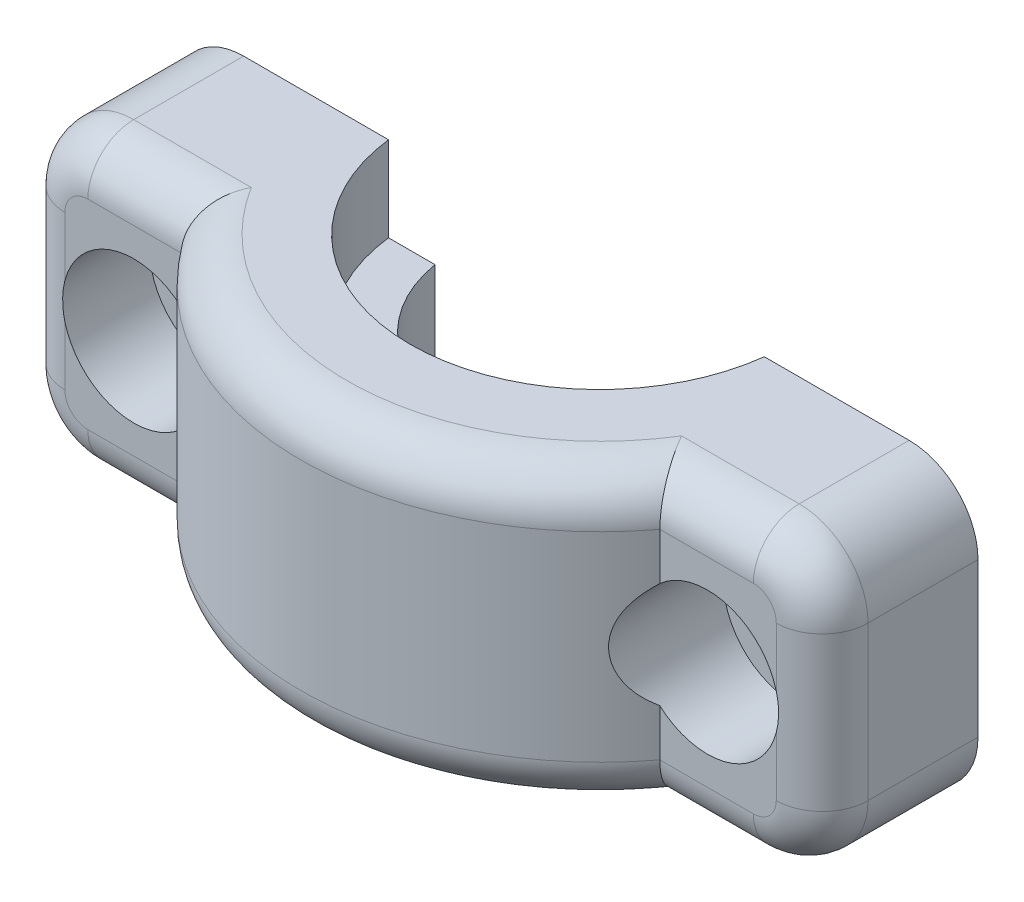
SolidWorks part; units mm, degrees
material "ABS"
ref_plane "Front Plane" through (0, 0, 0) normal (0, 0, 1) x (1, 0, 0)
ref_plane "Top Plane" through (0, 0, 0) normal (0, 1, 0) x (1, 0, 0)
ref_plane "Right Plane" through (0, 0, 0) normal (1, 0, 0) x (0, 0, -1)
sketch "Sketch1" plane through (0, 0, 0) normal (0, 0, 1) x (1, 0, 0)
  line L1 (-17.5, -6.35) -> (17.5, -6.35)
  line L2 (-17.5, -6.35) -> (-17.5, 6.35)
  line L3 (-17.5, 6.35) -> (17.5, 6.35)
  line L4 (17.5, -6.35) -> (17.5, 6.35)
  line L5 (-17.5, -6.35) -> (17.5, 6.35) construction
  line L6 (-17.5, 6.35) -> (17.5, -6.35) construction
  circle A0 centre (12.5, 0) radius 1.75
  circle A1 centre (-12.5, 0) radius 1.75
  point P0 (0, 0)
  dimension "D1" = 12.5
  dimension "D2" = 25
  dimension "D5" = 3.5
  dimension "D3" = 35
  dimension "D4" = 12.7
extrude "Boss-Extrude1" add sketch "Sketch1" along normal blind 12
sketch "Sketch2" plane through (0, 6.35, 0) normal (0, 1, 0) x (1, 0, 0)
  line L0 (17.5, 0) -> (-17.5, 0) construction
  circle A0 centre (0, 1) radius 8.25
  dimension "D2" = 16.5
  dimension "D1" = 1
extrude "Cut-Extrude1" cut sketch "Sketch2" against normal blind 3.7
sketch "Sketch3" plane through (0, 2.65, 0) normal (0, 1, 0) x (1, 0, 0)
  circle A0 centre (0, 1.0412) radius 6.25
  dimension "D1" = 12.5
extrude "Cut-Extrude2" cut sketch "Sketch3" against normal blind 5.7
sketch "Sketch4" plane through (0, -3.05, 0) normal (0, 1, 0) x (1, 0, 0)
  circle A0 centre (0, 1.0412) radius 8.25
  dimension "D1" = 16.5
extrude "Cut-Extrude3" cut sketch "Sketch4" against normal blind 6
sketch "Sketch5" plane through (0, 0, 12) normal (0, 0, 1) x (1, 0, 0)
  circle A0 centre (-12.5, 0) radius 3.1
  circle A1 centre (12.5, 0) radius 3.1
  dimension "D1" = 6.2
  dimension "D2" = 6.2
extrude "Cut-Extrude4" cut sketch "Sketch5" against normal offset from surface (9 mm away) 3 up to face at (10.009, -0.1, 0)
sketch "Sketch6" plane through (0, -6.35, 0) normal (0, -1, 0) x (1, 0, 0)
  line L0 (17.5, 0) -> (0, 0)
  line L1 (17.5, 0) -> (17.5, 6.7912)
  line L2 (17.5, 12) -> (17.5, 0) construction
  line L3 (17.5, 6.7912) -> (10.4272, 6.7912)
  line L4 (-17.5, 12) -> (-17.5, 0) construction
  line L5 (-17.5, 6.7912) -> (-17.5, 0)
  line L6 (-17.5, 0) -> (0, 0)
  line L7 (-10.4272, 6.7912) -> (-17.5, 6.7912)
  line L8 (-17.5, 12) -> (17.5, 12) construction
  line L9 (17.5, 6.7912) -> (17.5, 12)
  line L10 (17.5, 12) -> (-17.5, 12)
  line L11 (-17.5, 12) -> (-17.5, 6.7912)
  arc A0 (10.4272, 6.7912) -> (-10.4272, 6.7912) centre (0, -1.0412) ccw
  arc A3 (6.1627, 0) -> (-6.1627, 0) centre (0, -1.0412) ccw construction
  line M8 (17.5, 0) -> (17.5, 12)
  line M9 (17.5, 12) -> (-17.5, 12)
  line M10 (-17.5, 12) -> (-17.5, 0)
  dimension "D1" = 6.7912
  dimension "D2" = 6.7912
extrude "Cut-Extrude5" cut sketch "Sketch6" against normal blind 20 contours A0 L3 M8 M9 | A0 L10 L7 M10 region at (12.1102, -6.35, 9.7384) region at (-12.1102, -6.35, 9.7384)
fillet "Fillet1" radius 3 4 edges at (17.5, 6.35, 3.3956) (17.5, -6.35, 3.3956) (-17.5, -6.35, 3.3956) (-17.5, 6.35, 3.3956)
fillet "Fillet2" radius 2 12 edges at (-12.4636, 6.35, 6.7912) (-16.6213, 5.4713, 6.7912) (-17.5, 0, 6.7912) (-16.6213, -5.4713, 6.7912) (12.4636, 6.35, 6.7912) (16.6213, 5.4713, 6.7912) (17.5, 0, 6.7912) (16.6213, -5.4713, 6.7912) (0, 6.35, 12) (0, -6.35, 12) (-12.4636, -6.35, 6.7912) (12.4636, -6.35, 6.7912)
equation "\"D1@Sketch6\"=\"D2@Sketch6\""
equation "\"D2@Sketch5\"=\"D1@Sketch5\""
